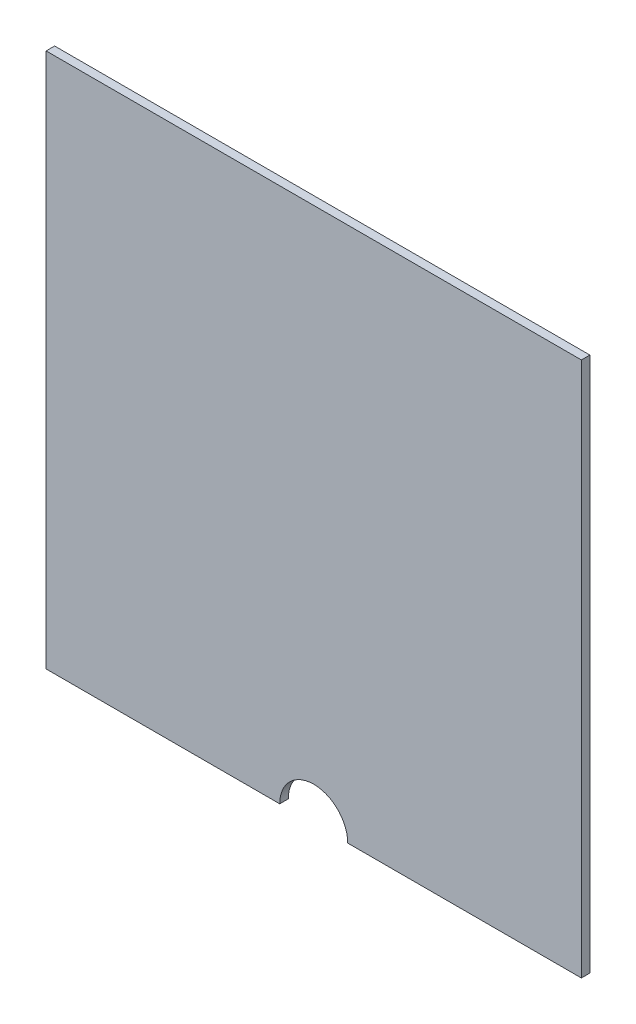
SolidWorks part; units mm, degrees
material "PVC Rigid"
ref_plane "Front Plane" through (0, 0, 0) normal (0, 0, 1) x (1, 0, 0)
ref_plane "Top Plane" through (0, 0, 0) normal (0, 1, 0) x (1, 0, 0)
ref_plane "Right Plane" through (0, 0, 0) normal (1, 0, 0) x (0, 0, -1)
sketch "Sketch1" plane through (0, 0, 0) normal (0, 0, 1) x (1, 0, 0)
  line L1 (0, 0) -> (199.873, 0)
  line L2 (0, 0) -> (0, 199.873)
  line L3 (0, 199.873) -> (199.873, 199.873)
  line L4 (199.873, 0) -> (199.873, 199.873)
  dimension "D1" = 199.873
extrude "Boss-Extrude1" add sketch "Sketch1" along normal blind 3.175
sketch "Sketch3" plane through (0, 0, 3.175) normal (0, 0, 1) x (1, 0, 0)
  line L0 (99.9365, 199.873) -> (99.9365, 0) construction
  line L1 (199.873, 199.873) -> (0, 199.873) construction
  line L2 (0, 0) -> (199.873, 0) construction
  line L3 (87.2365, 0) -> (112.6365, 0)
  arc A0 (112.6365, 0) -> (87.2365, 0) centre (99.9365, 0) ccw
  dimension "D1" = 25.4
extrude "Cut-Extrude3" cut sketch "Sketch3" against normal blind 3.175
sketch "Sketch4" plane through (0, 0, 3.175) normal (0, 0, 1) x (1, 0, 0)
  line L0 (2.54, 2.54) -> (199.873, 2.54) construction
  line L1 (199.873, 0) -> (199.873, 199.873) construction
  line L3 (0, 0) -> (2.54, 0) construction
  line L4 (0, 0) -> (0, 2.54) construction
  line L5 (0, 2.54) -> (2.54, 2.54) construction
  line L6 (2.54, 0) -> (2.54, 2.54) construction
  text T0 "SP_AGAR" font "Consolas" height 3.5
  dimension "D1" = 2.54
extrude "Cut-Extrude4" [suppressed] cut sketch "Sketch4" against normal blind 1.5875
